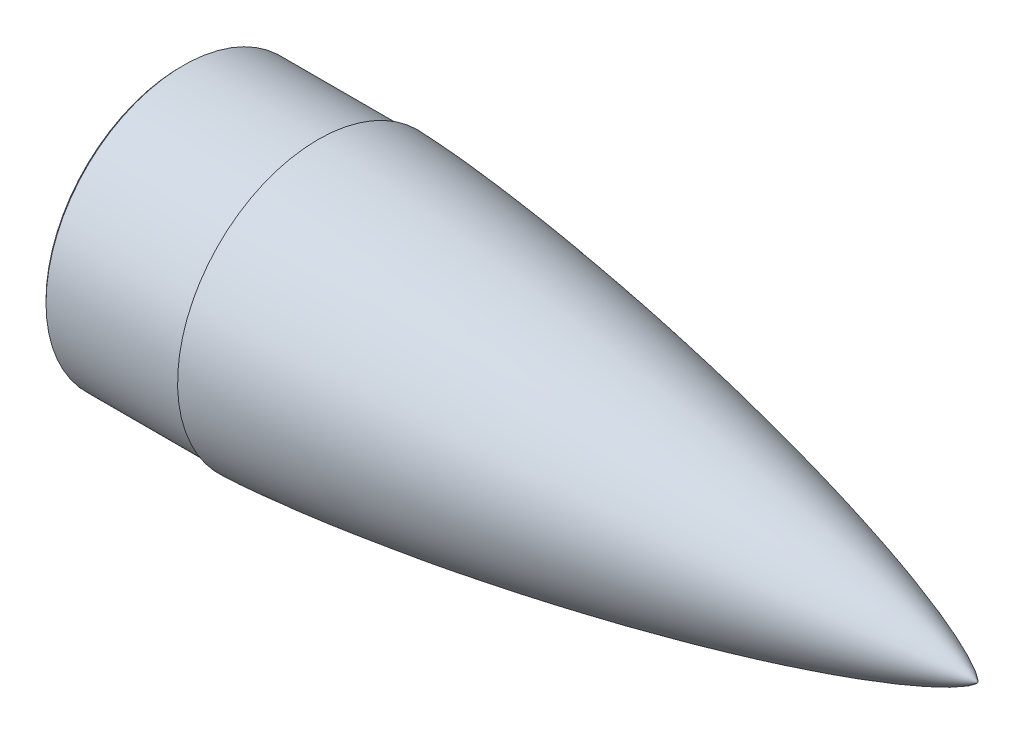
SolidWorks part; units mm, degrees
material "Plain Carbon Steel"
ref_plane "Front Plane" through (0, 0, 0) normal (0, 0, 1) x (1, 0, 0)
ref_plane "Top Plane" through (0, 0, 0) normal (0, 1, 0) x (1, 0, 0)
ref_plane "Right Plane" through (0, 0, 0) normal (1, 0, 0) x (0, 0, -1)
ref_axis "Axis1" through (46.9179, 0, 0) along (-1, 0, 0)
sketch "Sketch10" plane through (0, 0, 0) normal (0, 0, 1) x (1, 0, 0)
  line L1 (-1.0327, 0) -> (486.9547, 0) construction
  line L2 (11.1125, 81.9998) -> (11.1125, 67.4998)
  line L3 (11.1125, 81.9998) -> (-84.6045, 81.9998)
  line L4 (408.9673, 0) -> (368.9673, 0)
  line L5 (-84.6045, 81.9998) -> (-84.6045, 84.9998)
  line L6 (-84.6045, 84.9998) -> (0.3953, 84.9998)
  line L7 (0.3953, 84.9998) -> (0.3953, 86.9998)
  line L8 (11.1125, 67.4998) -> (129.3045, 67.4998)
  spline S0 degree 4 poles (408.9673, 0) (408.9649, 0.0135) (408.958, 0.0399) (408.9365, 0.0905) (408.8922, 0.1741) (408.8263, 0.2756) (408.7217, 0.4158) (408.5611, 0.6051) (408.3056, 0.8724) (407.8697, 1.2753) (407.121, 1.8851) (405.8038, 2.8259) (403.4624, 4.2872) (399.3253, 6.5318) (392.4811, 9.7589) (380.6621, 14.628) (363.6372, 20.7117) (342.2152, 27.4765) (317.4285, 34.4976) (291.8793, 41.1048) (266.2105, 47.229) (240.4455, 52.9334) (214.5989, 58.2554) (188.6809, 63.2176) (165.9462, 67.2533) (146.422, 70.4938) (130.1279, 73.0449) (117.0786, 74.9942) (104.0155, 76.8485) (92.5733, 78.3845) (82.7571, 79.6356) (74.5713, 80.6322) (68.0193, 81.4008) (61.4637, 82.1394) (54.9047, 82.8464) (48.3422, 83.5199) (41.7761, 84.1578) (36.0275, 84.6822) (31.0979, 85.1052) (26.9883, 85.4387) (23.6997, 85.6932) (20.0858, 85.9584) (16.7199, 86.189) (13.6021, 86.387) (10.7327, 86.5546) (8.4366, 86.6787) (6.14, 86.7922) (4.1299, 86.8793) (2.4065, 86.9446) (1.2573, 86.979) (0.6827, 86.9949) (0.3953, 86.9998) knots 0 0 0 0 0 0.00013 0.00026 0.00052 0.0009 0.00128 0.001925 0.002882 0.004418 0.006927 0.011111 0.018279 0.030673 0.051704 0.083102 0.139909 0.202703 0.265496 0.32829 0.391083 0.453877 0.516671 0.579464 0.642258 0.673655 0.705051 0.736448 0.767845 0.799242 0.81494 0.830639 0.846337 0.862036 0.877734 0.893432 0.909131 0.924829 0.932678 0.940527 0.948377 0.956226 0.967169 0.972641 0.978113 0.983585 0.989056 0.994528 0.997264 1 1 1 1 1 construction
  spline S1 degree 4 poles (408.9673, 0) (408.9649, 0.0135) (408.958, 0.0399) (408.9365, 0.0905) (408.8922, 0.1741) (408.8263, 0.2756) (408.7217, 0.4158) (408.5611, 0.6051) (408.3056, 0.8724) (407.8697, 1.2753) (407.121, 1.8851) (405.8038, 2.8259) (403.4624, 4.2872) (399.3253, 6.5318) (392.4811, 9.7589) (380.6621, 14.628) (363.6372, 20.7117) (342.2152, 27.4765) (317.4285, 34.4976) (291.8793, 41.1048) (266.2105, 47.229) (240.4455, 52.9334) (214.5989, 58.2554) (188.6809, 63.2176) (165.9462, 67.2533) (146.422, 70.4938) (130.1279, 73.0449) (117.0786, 74.9942) (104.0155, 76.8485) (92.5733, 78.3845) (82.7571, 79.6356) (74.5713, 80.6322) (68.0193, 81.4008) (61.4637, 82.1394) (54.9047, 82.8464) (48.3422, 83.5199) (41.7761, 84.1578) (36.0275, 84.6822) (31.0979, 85.1052) (26.9883, 85.4387) (23.6997, 85.6932) (20.0858, 85.9584) (16.7199, 86.189) (13.6021, 86.387) (10.7327, 86.5546) (8.4366, 86.6787) (6.14, 86.7922) (4.1299, 86.8793) (2.4065, 86.9446) (1.2573, 86.979) (0.6827, 86.9949) (0.3953, 86.9998) knots 0 0 0 0 0 0.00013 0.00026 0.00052 0.0009 0.00128 0.001925 0.002882 0.004418 0.006927 0.011111 0.018279 0.030673 0.051704 0.083102 0.139909 0.202703 0.265496 0.32829 0.391083 0.453877 0.516671 0.579464 0.642258 0.673655 0.705051 0.736448 0.767845 0.799242 0.81494 0.830639 0.846337 0.862036 0.877734 0.893432 0.909131 0.924829 0.932678 0.940527 0.948377 0.956226 0.967169 0.972641 0.978113 0.983585 0.989056 0.994528 0.997264 1 1 1 1 1
  spline S2 degree 4 poles (368.9673, 0) (368.9653, 0.0123) (368.9594, 0.0365) (368.9406, 0.083) (368.9023, 0.1587) (368.8455, 0.2503) (368.7557, 0.3766) (368.6167, 0.5484) (368.3929, 0.7936) (368.0087, 1.1649) (367.3447, 1.7299) (366.1761, 2.6016) (364.0928, 3.96) (360.426, 6.0407) (354.4022, 9.0183) (344.043, 13.5077) (329.152, 19.1285) (310.4252, 25.3986) (288.7413, 31.9337) (266.3785, 38.1061) (243.9014, 43.8469) (221.332, 49.212) (198.684, 54.2345) (175.9669, 58.9343) (156.0346, 62.7717) (138.9133, 65.8645) (124.6221, 68.3077) (113.1754, 70.1797) (101.7151, 71.9664) (91.6754, 73.4517) (83.0615, 74.6659) (75.8775, 75.6363) (70.1269, 76.3867) (64.3728, 77.1101) (58.6152, 77.8049) (52.854, 78.4695) (47.0892, 79.1019) (42.0417, 79.6247) (37.7129, 80.0488) (34.1039, 80.385) (31.2157, 80.6428) (28.0648, 80.911) (24.6507, 81.1843) (21.4654, 81.4195) (18.5093, 81.6177) (16.0448, 81.767) (14.3191, 81.8612) (12.8395, 81.9336) (11.8527, 81.9739) (11.3593, 81.993) (11.1125, 81.9998) knots 0 0 0 0 0 0.000135 0.00027 0.00054 0.00092 0.001299 0.001947 0.002931 0.004512 0.007081 0.01138 0.018708 0.031424 0.052705 0.084103 0.14091 0.203703 0.266497 0.329291 0.392084 0.454878 0.517672 0.580465 0.643259 0.674656 0.706052 0.737449 0.768846 0.800243 0.815941 0.831639 0.847338 0.863036 0.878735 0.894433 0.910132 0.92583 0.933679 0.941528 0.949378 0.957227 0.96792 0.978613 0.98396 0.989307 0.994653 0.997327 1 1 1 1 1 construction
  spline S3 degree 4 poles (368.9673, 0) (368.9653, 0.0123) (368.9594, 0.0365) (368.9406, 0.083) (368.9023, 0.1587) (368.8455, 0.2503) (368.7557, 0.3766) (368.6167, 0.5484) (368.3929, 0.7936) (368.0087, 1.1649) (367.3447, 1.7299) (366.1761, 2.6016) (364.0928, 3.96) (360.426, 6.0407) (354.4022, 9.0183) (344.043, 13.5077) (329.152, 19.1285) (310.4252, 25.3986) (288.7413, 31.9337) (266.3785, 38.1061) (243.9014, 43.8469) (221.332, 49.212) (198.684, 54.2345) (175.9669, 58.9343) (156.0346, 62.7717) (141.5091, 65.3956) (132.6794, 66.9245) (129.5628, 67.4559) (129.3045, 67.4998) knots 0 0 0 0 0 0.000135 0.00027 0.00054 0.00092 0.001299 0.001947 0.002931 0.004512 0.007081 0.01138 0.018708 0.031424 0.052705 0.084103 0.14091 0.203703 0.266497 0.329291 0.392084 0.454878 0.517672 0.580465 0.643259 0.674656 0.677492 0.677492 0.677492 0.677492 0.677492
  dimension "D1" = 86.9998
  dimension "D2" = 3
  dimension "D3" = 410
  dimension "D4" = 84.9998
  dimension "D5" = 370
  dimension "D6" = 84.9998
  dimension "D7" = 19.5
  dimension "D8" = 118.192
revolve "Revolve1" add sketch "Sketch10" angle 360 about axis through (46.9179, 0, 0) along (-1, 0, 0)
chamfer "Chamfer1" distance 1.5 angle 45 1 edges at (-84.6045, 0, -84.9998)
ref_plane "Plane1" through (70, 0, 0) normal (1, 0, 0) x (0, 0, -1)
sketch "Sketch11" plane through (70, 0, 0) normal (1, 0, 0) x (0, 0, -1)
  line L0 (39.6458, -13.0184) -> (39.6458, 13.0184)
  line L1 (-13.0184, -39.6458) -> (-13.0184, -66.2327)
  line L2 (-13.0184, -39.6458) -> (13.0184, -39.6458)
  line L3 (39.6458, -13.0184) -> (66.2327, -13.0184)
  line L4 (39.6458, 13.0184) -> (66.2327, 13.0184)
  line L5 (13.0184, -39.6458) -> (13.0184, -66.2327)
  line L6 (-39.6458, 13.0184) -> (-66.2327, 13.0184)
  line L7 (-39.6458, 13.0184) -> (-39.6458, -13.0184)
  line L8 (-39.6458, -13.0184) -> (-66.2327, -13.0184)
  line L9 (13.0184, 39.6458) -> (13.0184, 66.2327)
  line L10 (13.0184, 39.6458) -> (-13.0184, 39.6458)
  line L11 (-13.0184, 39.6458) -> (-13.0184, 66.2327)
  circle A0 centre (0, 0) radius 67.5
  circle A1 centre (0, 0) radius 67.5
  circle A2 centre (0, 0) radius 67.5
  circle A3 centre (0, 0) radius 67.5
  circle A4 centre (0, 52.1458) radius 5
  circle A5 centre (0, 0) radius 67.5
  circle A6 centre (52.1458, 0) radius 5
  circle A7 centre (0, 0) radius 67.5
  circle A8 centre (0, -52.1458) radius 5
  circle A9 centre (0, 0) radius 67.5
  circle A10 centre (-52.1458, 0) radius 5
  point P26 (0, 0)
  point P39 (0, 0)
  dimension "D1" = 4
  dimension "D2" = 4
extrude "Boss-Extrude6" add sketch "Sketch11" along normal blind 7.5 and the other way blind 7.5 contours L9 A0 L11 L10 | L3 A0 L4 L0 | L1 A0 L5 L2 | L6 A0 L8 L7 region at (70, 0, -40.027) region at (70, -67.1187, 0) region at (70, 52.9392, -12.6371) region at (70, 0, 67.1187)
sketch "Sketch16" plane through (0, 0, 0) normal (0, 0, 1) x (1, 0, 0)
  line L0 (93.213, 0.912) -> (93.213, 5)
  line L1 (93.213, 0.912) -> (93.213, -4.088)
  line L2 (93.213, -4.088) -> (98.213, -4.088)
  line L3 (93.213, 5) -> (98.213, 5)
  line L4 (98.213, -4.088) -> (98.213, 5)
extrude "Cut-Extrude1" cut sketch "Sketch16" against normal blind 95
